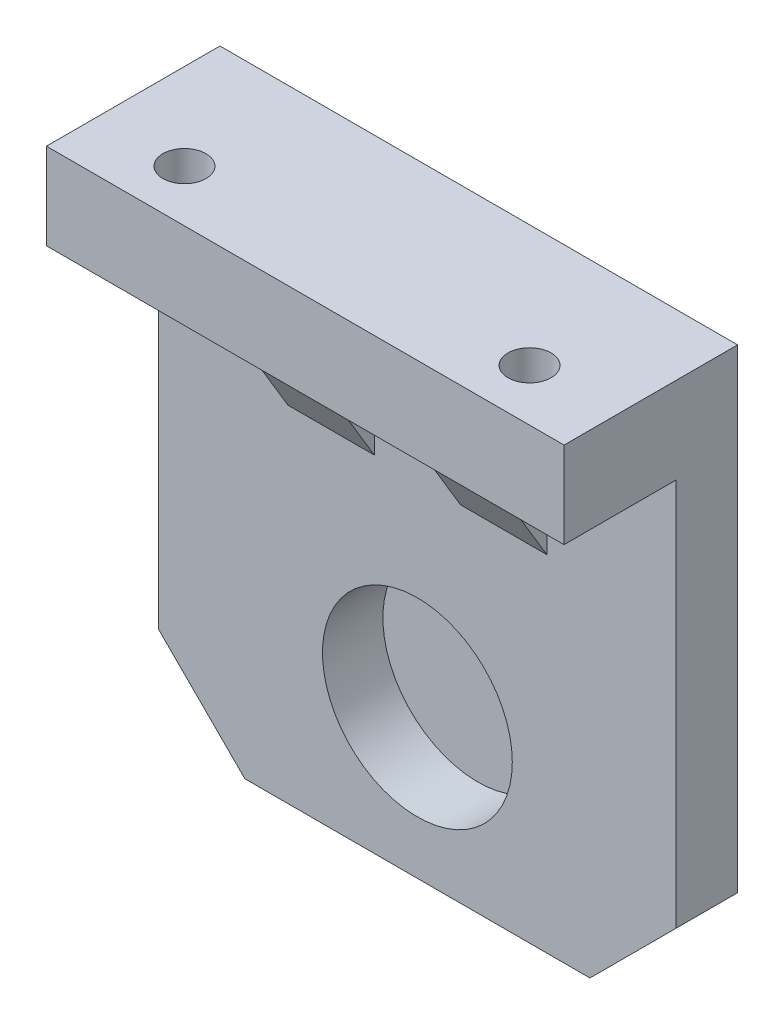
SolidWorks part; units mm, degrees
ref_plane "Plan de face" through (0, 0, 0) normal (0, 0, 1) x (1, 0, 0)
ref_plane "Plan de dessus" through (0, 0, 0) normal (0, 1, 0) x (1, 0, 0)
ref_plane "Plan de droite" through (0, 0, 0) normal (1, 0, 0) x (0, 0, -1)
sketch "Sketch1" plane through (0, 0, 0) normal (0, 0, 1) x (1, 0, 0)
  line L1 (30, 0) -> (90, 0)
  line L2 (30, 0) -> (30, 65)
  line L3 (30, 65) -> (90, 65)
  line L4 (90, 0) -> (90, 65)
  line L7 (-140, 65) -> (-140, 69) construction
  dimension "D1" = 60
  dimension "D2" = 65
  dimension "D3" = 170
  dimension "D4" = 65
extrude "Boss-Extrude1" add sketch "Sketch1" along normal blind 10
sketch "Sketch5" plane through (0, 0, 10) normal (0, 0, 1) x (1, 0, 0)
  line L1 (30, 0) -> (90, 0) construction
  line L2 (60, 0) -> (60, 65) construction
  line L3 (30, 0) -> (90, 0) construction
  line L4 (-140, 65) -> (260, 65) construction
  circle A0 centre (60, 17.17) radius 11
  dimension "D1" = 22
  dimension "D3" = 17.17
sketch "Sketch6" plane through (0, 0, 0) normal (0, 0, -1) x (-1, 0, 0)
  line L0 (-90, 0) -> (-90, 65) construction
  line L1 (-30, 65) -> (-90, 65)
  line L2 (-30, 65) -> (-30, 55)
  line L3 (-30, 55) -> (-90, 55)
  line L4 (-90, 65) -> (-90, 55)
  dimension "D1" = 10
extrude "Boss-Extrude2" add sketch "Sketch6" against normal blind 23
chamfer "Chamfer1" distance 5 angle 30 4 edges at (30, 32.5, 0) (60, 0, 0) (90, 32.5, 0) (60, 65, 0) first distance on face at (60, 32.5, 0)
extrude "Cut-Extrude4" cut sketch "Sketch5" against normal blind 7 contours A0
sketch "Sketch12" plane through (0, 55, 0) normal (0, -1, 0) x (-1, 0, 0)
  line L0 (-60, -23) -> (-60, -2.8868) construction
  line L1 (-90, -23) -> (-30, -23) construction
  line L2 (-30, -2.8868) -> (-90, -2.8868) construction
  circle A0 centre (-80, -17) radius 2.5
  circle A1 centre (-40, -17) radius 2.5
  dimension "D1" = 5
  dimension "D2" = 20
  dimension "D3" = 6
extrude "Cut-Extrude6" cut sketch "Sketch12" against normal through all
ref_plane "Plane1" through (50, 0, 0) normal (1, 0, 0) x (0, 0, -1)
ref_plane "Plane2" through (60, 0, 0) normal (1, 0, 0) x (0, 0, -1)
sketch "Sketch13" plane through (50, 0, 0) normal (1, 0, 0) x (0, 0, -1)
  line L0 (-19, 55) -> (-10, 40)
  line L1 (-23, 55) -> (-10, 55) construction
  line L2 (-10, 0) -> (-10, 55) construction
  dimension "D1" = 4
  dimension "D2" = 15
rib "Rib1" sketch "Sketch13" sketch "Sketch13" thickness 10 extrusion direction parallel to sketch draft on no parameters "D1"=10
mirror "Mirror1" about plane through (60, 0, 0) normal (1, 0, 0) of "Rib1"
chamfer "Chamfer3" distance 10 angle 45 2 edges at (90, 0, 6.4434) (30, 0, 6.4434)
sketch "Sketch14" plane through (30, 0, 0) normal (-1, 0, 0) x (0, 0, 1)
  line L0 (2.8868, 65) -> (2.8868, 10) construction
  line L2 (2.8868, 10) -> (10, 10) construction
  line L3 (4.8, 26.4) -> (4.8, 29.8) construction
  line L5 (4.8, 29.8) -> (14.3, 29.8) construction
  circle A0 centre (7.3, 24.6) radius 1.175
  circle A1 centre (7.3, 15.1) radius 1.25
  point P11 (4.1689, 10)
  point P16 (7.1488, 29.8)
  point P17 (7.2956, 24.7136)
  dimension "D1" = 2.35
  dimension "D2" = 2.5
  dimension "D3" = 4.4132
  dimension "D4" = 5.1
  dimension "D5" = 2.5
  dimension "D6" = 5.2
extrude "Cut-Extrude7" cut sketch "Sketch14" against normal blind 5
